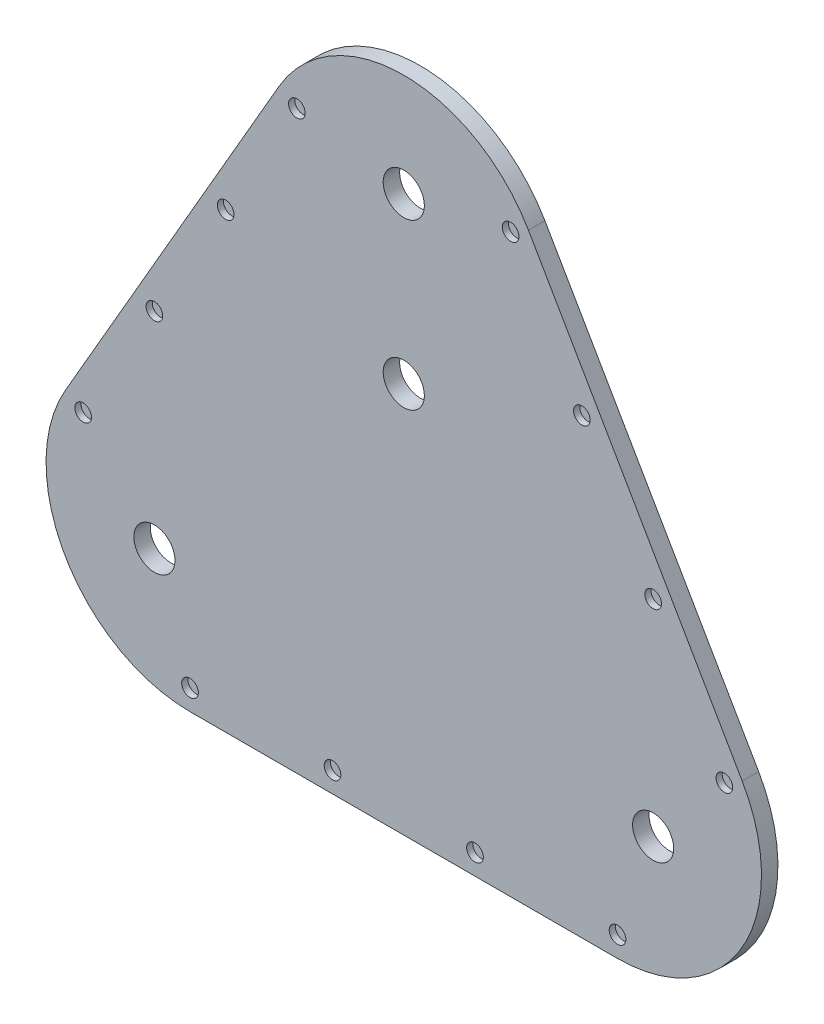
SolidWorks part; units mm, degrees
ref_plane "Plano frontal" through (0, 0, 0) normal (0, 0, 1) x (1, 0, 0)
ref_plane "Plano superior" through (0, 0, 0) normal (0, 1, 0) x (1, 0, 0)
ref_plane "Plano direito" through (0, 0, 0) normal (1, 0, 0) x (0, 0, -1)
sketch "Esboço1" plane through (0, 0, 0) normal (0, 0, 1) x (1, 0, 0)
  line L3 (-30.3109, 77.5) -> (-82.2724, -12.5)
  line L4 (-51.9615, -65) -> (51.9615, -65)
  line L5 (82.2724, -12.5) -> (30.3109, 77.5)
  arc A3 (-82.2724, -12.5) -> (-51.9615, -65) centre (-51.9615, -30) ccw
  arc A4 (51.9615, -65) -> (82.2724, -12.5) centre (51.9615, -30) ccw
  arc A5 (30.3109, 77.5) -> (-30.3109, 77.5) centre (0, 60) ccw
extrude "Ressalto-extrusão1" add sketch "Esboço1" along normal blind 4
sketch "Esboço2" plane through (0, 0, 0) normal (0, 0, 1) x (1, 0, 0)
  line L0 (0, 0) -> (0, 70) construction
  circle A3 centre (0, 70) radius 5
  circle A4 centre (60.6218, -35) radius 5
  circle A5 centre (-60.6218, -35) radius 5
  circle A6 centre (0, 30) radius 5
  point P13 (0, 0)
  dimension "D1" = 70
  dimension "D2" = 10
  dimension "D4" = 10
  dimension "D5" = 30
  dimension "D3" = 3
extrude "Corte-extrusão1" cut sketch "Esboço2" along normal up to surface (4 mm away) up to face at (0, 0, 4)
sketch "Esboço3" plane through (0, 0, 4) normal (0, 0, 1) x (1, 0, 0)
  line L0 (-25.9808, 75) -> (-77.9423, -15) construction
  line L1 (-51.9615, -60) -> (51.9615, -60) construction
  line L2 (77.9423, -15) -> (25.9808, 75) construction
  line L3 (-30.3109, 77.5) -> (-82.2724, -12.5)
  line L4 (-51.9615, -65) -> (51.9615, -65)
  line L5 (82.2724, -12.5) -> (30.3109, 77.5)
  line L6 (-30.3109, 77.5) -> (-82.2724, -12.5) construction
  line L7 (-51.9615, -65) -> (51.9615, -65) construction
  line L8 (82.2724, -12.5) -> (30.3109, 77.5) construction
  arc A0 (-77.9423, -15) -> (-51.9615, -60) centre (-51.9615, -30) ccw construction
  arc A1 (51.9615, -60) -> (77.9423, -15) centre (51.9615, -30) ccw construction
  arc A2 (25.9808, 75) -> (-25.9808, 75) centre (0, 60) ccw construction
  arc A3 (30.3109, 77.5) -> (-30.3109, 77.5) centre (0, 60) ccw
  arc A4 (-82.2724, -12.5) -> (-51.9615, -65) centre (-51.9615, -30) ccw
  arc A5 (51.9615, -65) -> (82.2724, -12.5) centre (51.9615, -30) ccw
  arc A6 (30.3109, 77.5) -> (-30.3109, 77.5) centre (0, 60) ccw construction
  arc A7 (-82.2724, -12.5) -> (-51.9615, -65) centre (-51.9615, -30) ccw construction
  arc A8 (51.9615, -65) -> (82.2724, -12.5) centre (51.9615, -30) ccw construction
  circle A9 centre (-77.9423, -15) radius 2.025
  circle A10 centre (-51.9615, -60) radius 2.025
  circle A11 centre (77.9423, -15) radius 2.025
  circle A12 centre (-60.6223, 14.9991) radius 2.025
  circle A13 centre (-43.3023, 44.9982) radius 2.025
  circle A14 centre (-25.9823, 74.9974) radius 2.025
  circle A15 centre (60.6223, 14.9991) radius 2.025
  circle A16 centre (43.3023, 44.9982) radius 2.025
  circle A17 centre (25.9823, 74.9974) radius 2.025
  circle A18 centre (-17.3215, -60) radius 2.025
  circle A19 centre (17.3185, -60) radius 2.025
  circle A20 centre (51.9585, -60) radius 2.025
  dimension "D3" = 4.05
  dimension "D1" = 0
  dimension "D2" = 5
  dimension "D4" = 4
  dimension "D5" = 4
  dimension "D6" = 4
extrude "Corte-extrusão2" cut sketch "Esboço3" against normal blind 1.5
